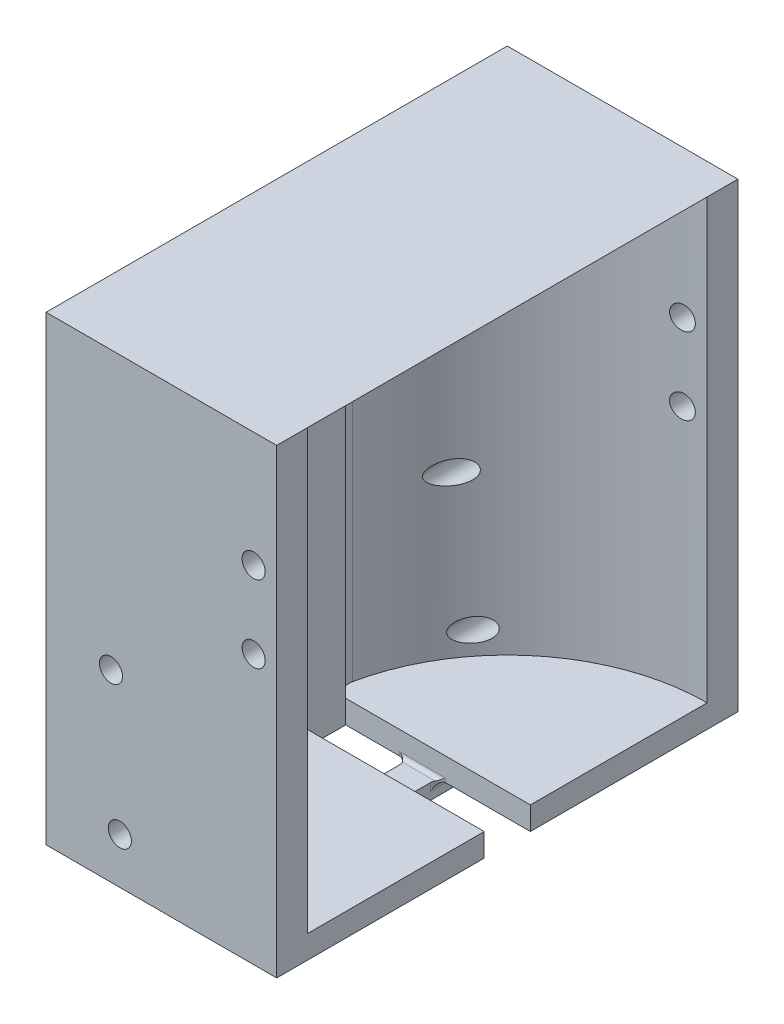
SolidWorks part; units mm, degrees
ref_plane "Front Plane" through (0, 0, 0) normal (0, 0, 1) x (1, 0, 0)
ref_plane "Top Plane" through (0, 0, 0) normal (0, 1, 0) x (1, 0, 0)
ref_plane "Right Plane" through (0, 0, 0) normal (1, 0, 0) x (0, 0, -1)
sketch "Sketch1" plane through (0, 0, 0) normal (0, 1, 0) x (1, 0, 0)
  line L0 (0, 30) -> (0, -30)
  line L1 (0, 30) -> (0, -30)
  line L2 (0, 30) -> (-30, 30)
  line L3 (0, -30) -> (-30, -30)
  line L4 (-30, 30) -> (-30, -30)
  arc A0 (0, 30) -> (0, -30) centre (0, 0) ccw
  arc A1 (0, 26) -> (0, -26) centre (0, 0) ccw
extrude "Boss-Extrude1" add sketch "Sketch1" along normal blind 60 contours A1 L0 A0 | L0 A1 region at (-0.6708, 0, -28) region at (-11.0347, 0, 0)
extrude "Boss-Extrude2" add sketch "Sketch1<3>" along normal blind 60 contours A0 L2 L4 | A0 L4 L3 region at (-23.299, 0, -23.299) region at (-23.299, 0, 23.299)
sketch "Sketch1<3>" plane through (0, 0, 0) normal (0, 1, 0) x (1, 0, 0) same geometry as "Sketch1"
extrude "Cut-Extrude1" cut sketch "Sketch1<4>" along normal blind 54 from offset 3 contours L1 A1 region at (-11.0347, 0, 0)
sketch "Sketch1<4>" plane through (0, 0, 0) normal (0, 1, 0) x (1, 0, 0) same geometry as "Sketch1"
sketch "Sketch2" plane through (0, 0, 0) normal (0, -1, 0) x (1, 0, 0)
  line L9 (-24.0196, -3) -> (-24.0196, 3)
  line L10 (-24.0196, -3) -> (0.0865, -3)
  line L11 (-24.0196, 3) -> (0.0865, 3)
  line L12 (0.0865, -3) -> (0.0865, 3)
extrude "Cut-Extrude2" cut sketch "Sketch2" against normal up to next
sketch "Sketch3" plane through (-24.0196, 0, 0) normal (1, 0, 0) x (0, 0, -1)
  line L0 (3, 0) -> (-3, 0)
  line L1 (3, 0) -> (3, 60)
  line L2 (-3, 0) -> (-3, 60)
  line L3 (3, 60) -> (-3, 60)
extrude "Boss-Extrude3" add sketch "Sketch3" against normal up to next
fillet "Fillet1" radius 2 2 edges at (-25.8263, 30, -3) (-25.8263, 30, 3)
sketch "Sketch4" plane through (0, 0, 0) normal (0, 0, 1) x (1, 0, 0)
  circle A0 centre (-20.4039, 5.9724) radius 1.5
  circle A1 centre (-21.5544, 23.9356) radius 1.5
extrude "Cut-Extrude3" cut sketch "Sketch4" against normal through all both and the other way through all
sketch "Sketch5" plane through (0, 0, 0) normal (0, 0, 1) x (1, 0, 0)
  circle A0 centre (-3, 35) radius 1.5
  circle A1 centre (-3, 45) radius 1.5
extrude "Cut-Extrude4" cut sketch "Sketch5" against normal through all both and the other way through all
chamfer "Chamfer1" distance 3 angle 70 1 edges at (0, 57, 0) first distance on face at (0, 20.5, 0)
sketch "Sketch6" plane through (0, 0, 0) normal (0, -1, 0) x (1, 0, 0)
  line L11 (-12.0098, -5) -> (-16.0196, -5)
  line L12 (-12.0098, -5) -> (-12.0098, 5)
  line L13 (-16.0196, -5) -> (-16.0196, 5)
  line L14 (-12.0098, 5) -> (-16.0196, 5)
extrude "Boss-Extrude4" add sketch "Sketch6" along normal blind 2
fillet "Fillet3" radius 0.5 2 edges at (-14.0147, 0, 3) (-14.0147, 0, -3)
fillet "Fillet4" radius 1 10 edges at (-12.0098, 0.25, 3) (-12.0098, 0.25, -3) (-16.0196, 0.25, -3) (-16.0196, 0.25, 3) (-16.0196, 0, 4) (-14.0147, 0, 5) (-12.0098, 0, 4) (-16.0196, 0, -4) (-14.0147, 0, -5) (-12.0098, 0, -4)
